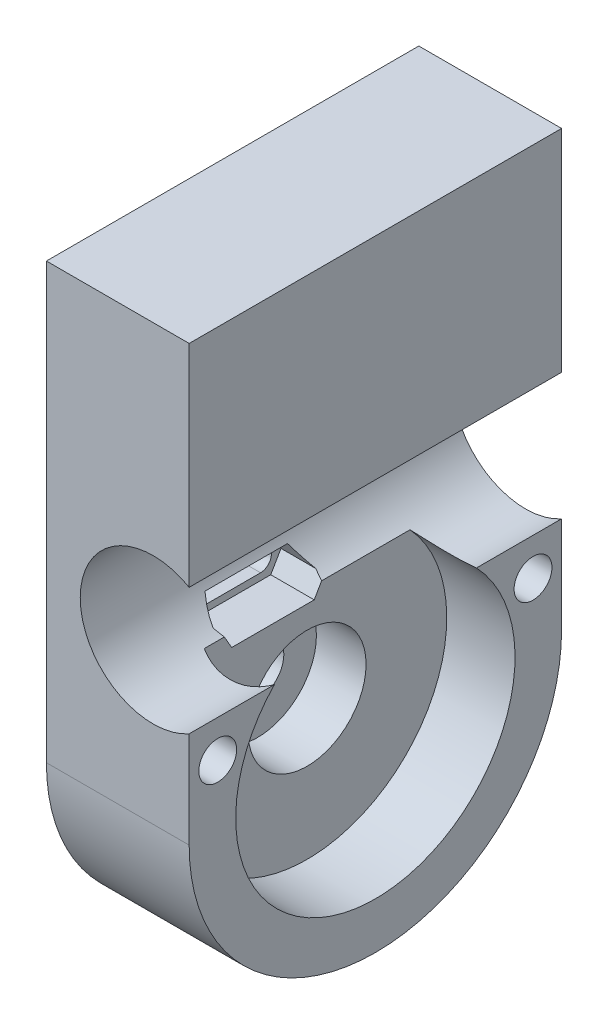
SolidWorks part; units mm, degrees
ref_plane "Front Plane" through (0, 0, 0) normal (0, 0, 1) x (1, 0, 0)
ref_plane "Top Plane" through (0, 0, 0) normal (0, 1, 0) x (1, 0, 0)
ref_plane "Right Plane" through (0, 0, 0) normal (1, 0, 0) x (0, 0, -1)
sketch "Sketch1" plane through (0, 0, 0) normal (1, 0, 0) x (0, 0, -1)
  line L1 (-30, 50) -> (30, 50)
  line L2 (-30, 50) -> (-30, -50)
  line L3 (-30, -50) -> (30, -50)
  line L4 (30, 50) -> (30, -50)
  line L5 (-30, 50) -> (30, -50) construction
  line L6 (-30, -50) -> (30, 50) construction
  point P0 (0, 0)
  dimension "D1" = 60
  dimension "D2" = 100
extrude "Boss-Extrude1" add sketch "Sketch1" along normal blind 23
sketch "Sketch2" plane through (23, 0, 0) normal (1, 0, 0) x (0, 0, -1)
  line L0 (0, 50) -> (0, -50) construction
  line L1 (30, 50) -> (-30, 50) construction
  line L2 (-30, -50) -> (30, -50) construction
  line L3 (0, -20) -> (-30, -20) construction
  line L4 (-30, 50) -> (-30, -50) construction
  line L5 (0, -20) -> (0, -50) construction
  circle A0 centre (0, -20) radius 22.5
  dimension "D1" = 45
extrude "Cut-Extrude1" cut sketch "Sketch2" against normal offset from surface (11 mm away) 12 up to face at (0, 0, 0)
sketch "Sketch3" plane through (0, 0, -30) normal (0, 0, -1) x (-1, 0, 0)
  line L0 (-17.2, 50) -> (-17.2, -50) construction
  line L1 (-23, 50) -> (0, 50) construction
  line L2 (-23, -50) -> (0, -50) construction
  line L3 (-23, 2.5) -> (-23, -42.5) construction
  line L4 (-23, 2.5) -> (-23, -42.5) construction
  line L5 (-23, -20) -> (0, -20) construction
  line L6 (0, -50) -> (0, 50) construction
  line L7 (0, 0) -> (-23, 0) construction
  line L8 (-23, -6) -> (0, -6) construction
  circle A0 centre (-17.2, 5.75) radius 11.75
  dimension "D1" = 23.5
  dimension "D2" = 20
  dimension "D3" = 6
  dimension "D4" = 17.2
extrude "Cut-Extrude2" cut sketch "Sketch3" against normal through all
sketch "Sketch4" plane through (12, 0, 0) normal (1, 0, 0) x (0, 0, -1)
  circle A0 centre (0, -20) radius 9.5
  dimension "D1" = 19
extrude "Cut-Extrude3" cut sketch "Sketch4" against normal offset from surface (8 mm away) 4 up to face at (0, 0, 0)
sketch "Sketch6" plane through (4, 0, 0) normal (1, 0, 0) x (0, 0, -1)
  circle A0 centre (0, -20) radius 4.25
  dimension "D1" = 8.5
extrude "Cut-Extrude5" cut sketch "Sketch6" against normal through all
ref_plane "Plane1" through (5, 0, 0) normal (-1, 0, 0) x (0, 0, 1)
sketch "Sketch7" plane through (5, 0, 0) normal (-1, 0, 0) x (0, 0, 1)
  line L0 (10.5, -4) -> (0.5, -4) construction
  line L1 (8.8546, -1.15) -> (2.1454, -1.15)
  line L2 (8.8546, -1.15) -> (7.2091, -4) construction
  line L3 (7.2091, -4) -> (8.8546, -6.85) construction
  line L4 (8.8546, -6.85) -> (12.1454, -6.85)
  line L5 (12.1454, -6.85) -> (13.7909, -4)
  line L6 (13.7909, -4) -> (12.1454, -1.15)
  line L7 (12.1454, -1.15) -> (8.8546, -1.15)
  line L8 (2.1454, -6.85) -> (3.7909, -4) construction
  line L9 (3.7909, -4) -> (2.1454, -1.15) construction
  line L10 (2.1454, -1.15) -> (-1.1454, -1.15)
  line L11 (-1.1454, -1.15) -> (-2.7909, -4)
  line L12 (-2.7909, -4) -> (-1.1454, -6.85)
  line L13 (-1.1454, -6.85) -> (2.1454, -6.85)
  line L14 (2.1454, -6.85) -> (8.8546, -6.85)
  line L15 (0, 50) -> (0, -50) construction
  line L16 (-30, 50) -> (30, 50) construction
  line L17 (30, -50) -> (-30, -50) construction
  circle A0 centre (10.5, -4) radius 2.85 construction
  circle A1 centre (0.5, -4) radius 2.85 construction
  arc A2 (-16.2797, -4.4687) -> (16.2797, -4.4687) centre (0, -20) ccw construction
  arc A3 (-16.2797, -4.4687) -> (16.2797, -4.4687) centre (0, -20) ccw construction
  point P2 (5.255, -6.5)
  point P26 (5.5, -4)
  dimension "D1" = 5.7
  dimension "D2" = 10
  dimension "D3" = 16
  dimension "D4" = 5.5
extrude "Cut-Extrude6" cut sketch "Sketch7" against normal through all
sketch "Sketch8" plane through (5, 0, 0) normal (-1, 0, 0) x (0, 0, 1)
  line L0 (10.5, -4) -> (0.5, -4) construction
  line L1 (10.5, -5.75) -> (0.5, -5.75)
  line L2 (10.5, -2.25) -> (0.5, -2.25)
  line L10 (8.8546, -1.15) -> (2.1454, -1.15)
  line L11 (2.1454, -1.15) -> (-1.1454, -1.15)
  line L12 (-1.1454, -1.15) -> (-2.7909, -4)
  line L13 (-2.7909, -4) -> (-1.1454, -6.85)
  line L14 (-1.1454, -6.85) -> (2.1454, -6.85)
  line L15 (2.1454, -6.85) -> (8.8546, -6.85)
  line L16 (8.8546, -6.85) -> (12.1454, -6.85)
  line L17 (12.1454, -6.85) -> (13.7909, -4)
  line L18 (13.7909, -4) -> (12.1454, -1.15)
  line L19 (12.1454, -1.15) -> (8.8546, -1.15)
  line L20 (8.8546, -1.15) -> (2.1454, -1.15) construction
  line L21 (2.1454, -1.15) -> (-1.1454, -1.15) construction
  line L22 (-1.1454, -1.15) -> (-2.7909, -4) construction
  line L23 (-2.7909, -4) -> (-1.1454, -6.85) construction
  line L24 (-1.1454, -6.85) -> (2.1454, -6.85) construction
  line L25 (2.1454, -6.85) -> (8.8546, -6.85) construction
  line L26 (8.8546, -6.85) -> (12.1454, -6.85) construction
  line L27 (12.1454, -6.85) -> (13.7909, -4) construction
  line L28 (13.7909, -4) -> (12.1454, -1.15) construction
  line L29 (12.1454, -1.15) -> (8.8546, -1.15) construction
  arc A0 (10.5, -5.75) -> (10.5, -2.25) centre (10.5, -4) ccw
  arc A1 (0.5, -2.25) -> (0.5, -5.75) centre (0.5, -4) ccw
  circle A2 centre (10.5, -4) radius 2.85 construction
  circle A3 centre (0.5, -4) radius 2.85 construction
  point P2 (5.5, -4)
  dimension "D2" = 3.5
  dimension "D1" = 0
extrude "Cut-Extrude7" cut sketch "Sketch8" against normal through all both and the other way through all
sketch "Sketch9" plane through (23, 0, 0) normal (1, 0, 0) x (0, 0, -1)
  line L0 (-30, -4.4687) -> (-30, -50) construction
  line L1 (30, -50) -> (30, -4.4687) construction
  line L2 (-30, -20) -> (-30, -50)
  line L3 (-30, -50) -> (0, -50)
  line L4 (30, -50) -> (30, -20)
  line L5 (-30, -20) -> (30, -20) construction
  line L6 (0, -50) -> (30, -50)
  line L7 (-25.4, -10.4687) -> (25.4, -10.4687) construction
  line L8 (27.2, -10.4687) -> (30, -10.4687) construction
  line L10 (-30, -10.4687) -> (-27.2, -10.4687) construction
  line L11 (-30, -4.4687) -> (-16.2797, -4.4687) construction
  arc A0 (-30, -20) -> (30, -20) centre (0, -20) ccw
  circle A1 centre (-25.4, -10.4687) radius 1.8
  circle A2 centre (25.4, -10.4687) radius 1.8
  dimension "D1" = 3.6
  dimension "D2" = 2.8
  dimension "D3" = 6
extrude "Cut-Extrude8" cut sketch "Sketch9" against normal through all contours A0 L2 L3 | A0 L6 L4 | A1 | A2 region at (23, -43.299, 23.299) region at (23, -43.299, -23.299) region at (23, -10.4687, 25.4)
sketch "Sketch10" plane through (23, 0, 0) normal (1, 0, 0) x (0, 0, -1)
  circle A0 centre (-25.4, -10.4687) radius 3.05
  circle A1 centre (25.4, -10.4687) radius 3.05
  dimension "D1" = 6.1
extrude "Cut-Extrude9" cut sketch "Sketch10" against normal offset from surface (18 mm away) 5 up to face at (0, -10.4687, -27.2)
